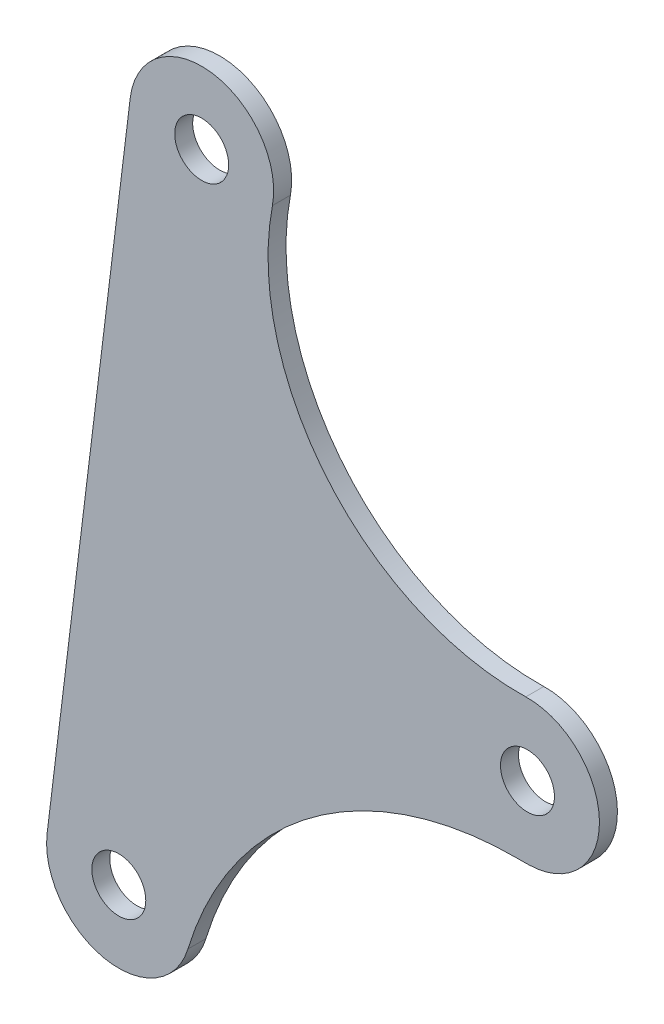
SolidWorks part; units mm, degrees
ref_plane "Front Plane" through (0, 0, 0) normal (0, 0, 1) x (1, 0, 0)
ref_plane "Top Plane" through (0, 0, 0) normal (0, 1, 0) x (1, 0, 0)
ref_plane "Right Plane" through (0, 0, 0) normal (1, 0, 0) x (0, 0, -1)
sketch "Esquisse1" plane through (0, 0, 0) normal (0, 0, 1) x (1, 0, 0)
  line L0 (-54.4842, -22.2361) -> (-49.8765, 15.4835) construction
  line L1 (-58.4693, -21.748) -> (-53.8489, 15.9701)
  arc A0 (-54.4842, -22.2361) -> (-31.7651, -5.8702) centre (-32.4019, -28.9383) cw construction
  arc A2 (-32.2973, -9.8767) -> (-50.6422, -23.4022) centre (-32.4019, -28.9383) ccw
  arc A5 (-49.8765, 15.4835) -> (-31.7651, -5.8702) centre (-32.1765, 12.1384) ccw construction
  arc A7 (-45.944, 14.7403) -> (-31.8565, -1.8691) centre (-32.1765, 12.1384) ccw
  arc A9 (-31.6737, -9.8712) -> (-31.8565, -1.8691) centre (-31.7651, -5.8702) ccw
  arc A10 (-58.4693, -21.748) -> (-50.6422, -23.4022) centre (-54.4842, -22.2361) ccw
  arc A11 (-45.944, 14.7403) -> (-53.8489, 15.9701) centre (-49.8765, 15.4835) ccw
  circle A12 centre (-54.4842, -22.2361) radius 1.5
  circle A13 centre (-31.7651, -5.8702) radius 1.5
  circle A14 centre (-49.8765, 15.4835) radius 1.5
  arc A16 (-32.2973, -9.8767) -> (-31.6737, -9.8712) centre (-32.1765, 12.1384) ccw
  point P3 (-42.9287, 2.3237)
  point P10 (-35.7876, 7.6907)
  point P21 (-43.6045, 10.9473)
  dimension "D2" = 8
  dimension "D3" = 8.0042
  dimension "D4" = 3
  dimension "D1" = 8
base flange "Tôle de base pliée1" sketch "Esquisse1" thickness 1 reverse thickness direction yes parameters "D1"=0.7366
sketch "Bend-Lines1" [suppressed] plane through (0, 0, 0) normal (0, 1, 0) x (1, 0, 0)
sketch "Bounding-Box1" [suppressed] plane through (0, 0, 0) normal (0, 1, 0) x (1, 0, 0)
sheet metal parameters "Sheet-Metal1" thickness 1 parameters "D1"=0.7366
flat pattern "Flat-Pattern1" [suppressed]
sketch "Bend-Lines2" plane through (0, 0, 0) normal (0, 1, 0) x (1, 0, 0)
sketch3d "Bounding-Box2" [suppressed]
  line L0 (-5.0711, 43.3601, 0) -> (-28.3598, 15.9026, 0) construction
  line L1 (22.3295, 20.1196, 0) -> (-0.9592, -7.3379, 0) construction
  line L2 (-5.0711, 43.3601, 0) -> (22.3295, 20.1196, 0) construction
  line L3 (-28.3598, 15.9026, 0) -> (-0.9592, -7.3379, 0) construction
